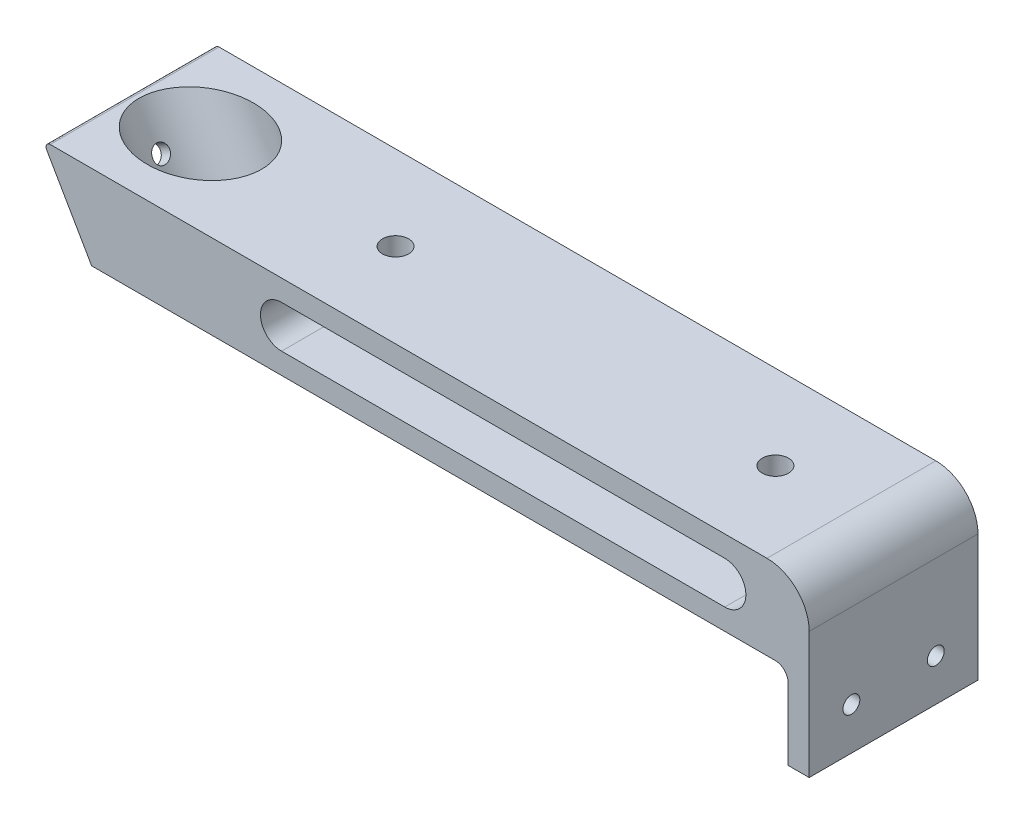
SolidWorks part; units mm, degrees
ref_plane "前视基准面" through (0, 0, 0) normal (0, 0, 1) x (1, 0, 0)
ref_plane "上视基准面" through (0, 0, 0) normal (0, 1, 0) x (1, 0, 0)
ref_plane "右视基准面" through (0, 0, 0) normal (1, 0, 0) x (0, 0, -1)
sketch "草图1" plane through (0, 0, 0) normal (0, 0, 1) x (1, 0, 0)
  line L0 (0, 0) -> (170, 0)
  line L1 (170, 0) -> (170, 20)
  line L2 (170, 20) -> (-11.547, 20)
  line L3 (-11.547, 20) -> (0, 0)
  line L4 (0, 0) -> (0, 151.1702) construction
  dimension "D1" = 30
  dimension "D2" = 20
  dimension "D3" = 170
extrude "凸台-拉伸1" add sketch "草图1" along normal blind 40
ref_plane "基准面1" through (-11.547, 20, 0) normal (-0.5, 0.866, 0) x (0, 0, -1)
sketch "草图2" plane through (-11.547, 20, 0) normal (-0.5, 0.866, 0) x (0, 0, -1)
  line L0 (0, 0) -> (-84.5846, 0) construction
  line L1 (0, -157.2243) -> (0, 0) construction
  circle A0 centre (-20, -15) radius 12.6
  dimension "D3" = 25.2
  dimension "D1" = 20
  dimension "D2" = 15
extrude "切除-拉伸1" cut sketch "草图2" against normal through all
sketch "草图3" plane through (0, 0, 0) normal (-0.866, -0.5, 0) x (0, 0, 1)
  line L0 (0, 0) -> (0, 49.6712) construction
  circle A0 centre (20, 11.4672) radius 2
  dimension "D2" = 4
  dimension "D1" = 40
extrude "切除-拉伸2" cut sketch "草图3" against normal up to next
sketch "草图4" plane through (0, 0, 0) normal (0, -1, 0) x (1, 0, 0)
  line L0 (0, 0) -> (170, 0) construction
  line L1 (170, 40) -> (165, 40)
  line L2 (170, 40) -> (170, 0)
  line L3 (170, 0) -> (165, 0)
  line L4 (165, 40) -> (165, 0)
  dimension "D1" = 5
extrude "凸台-拉伸2" add sketch "草图4" along normal blind 20
sketch "草图5" plane through (165, 0, 0) normal (-1, 0, 0) x (0, 0, 1)
  line L0 (20, 0) -> (20, -29.3991) construction
  line L1 (40, 0) -> (0, 0) construction
  line L2 (10, -10) -> (30, -10) construction
  circle A0 centre (10, -10) radius 2
  circle A1 centre (30, -10) radius 2
  dimension "D1" = 20
  dimension "D3" = 4
  dimension "D2" = 10
extrude "切除-拉伸3" cut sketch "草图5" against normal through all
fillet "圆角1" radius 10 1 edges at (170, 20, 20)
fillet "圆角2" radius 3 1 edges at (165, 0, 20)
sketch "草图6" plane through (0, 0, 0) normal (0, 0, -1) x (-1, 0, 0)
  line L0 (-150, 10) -> (-45, 10) construction
  line L1 (-150, 15) -> (-45, 15)
  line L2 (-150, 5) -> (-45, 5)
  line L3 (-160, 20) -> (11.547, 20) construction
  line L4 (-165, -20) -> (-165, -3) construction
  line L5 (0, 0) -> (0, 35.4113) construction
  arc A0 (-150, 15) -> (-150, 5) centre (-150, 10) ccw
  arc A1 (-45, 5) -> (-45, 15) centre (-45, 10) ccw
  point P2 (-97.5, 10)
  dimension "D1" = 10
  dimension "D2" = 5
  dimension "D3" = 15
  dimension "D4" = 45
extrude "切除-拉伸4" cut sketch "草图6" against normal through all
sketch "草图7" plane through (0, 0, 0) normal (0, -1, 0) x (1, 0, 0)
  line L0 (0, 20) -> (162, 20) construction
  line L1 (0, 40) -> (0, 0) construction
  line L2 (162, 0) -> (162, 40) construction
  circle A0 centre (52, 20) radius 3.1
  circle A1 centre (142, 20) radius 3.1
  dimension "D1" = 6.2
  dimension "D2" = 6.2
  dimension "D3" = 90
  dimension "D4" = 20
extrude "切除-拉伸5" cut sketch "草图7" against normal through all
sketch "草图8" plane through (0, 0, 0) normal (0, -1, 0) x (1, 0, 0)
  line L0 (55.1, 20) -> (138.9, 20) construction
  line L2 (50, 30) -> (144, 30)
  line L3 (47, 27) -> (47, 13)
  line L4 (50, 10) -> (144, 10)
  line L5 (147, 27) -> (147, 13)
  line L6 (47, 30) -> (147, 10) construction
  line L7 (47, 10) -> (147, 30) construction
  circle A0 centre (52, 20) radius 3.1 construction
  circle A1 centre (142, 20) radius 3.1 construction
  arc A2 (144, 30) -> (147, 27) centre (144, 27) cw
  arc A3 (144, 10) -> (147, 13) centre (144, 13) ccw
  arc A4 (47, 13) -> (50, 10) centre (50, 13) ccw
  arc A5 (47, 27) -> (50, 30) centre (50, 27) cw
  point P7 (97, 20)
  dimension "D3" = 3
  dimension "D1" = 20
  dimension "D2" = 100
extrude "切除-拉伸6" cut sketch "草图8" against normal up to next
fillet "圆角3" radius 1 1 edges at (-11.547, 20, 20)
